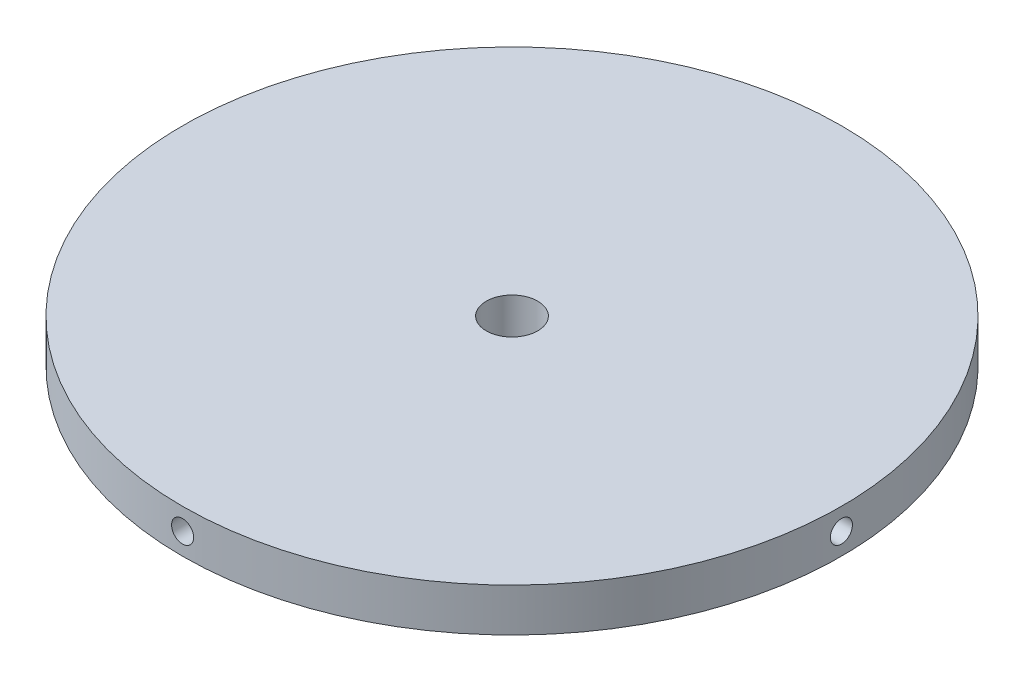
SolidWorks part; units mm, degrees
material "6061-T6 (SS)"
ref_plane "Front Plane" through (0, 0, 0) normal (0, 0, 1) x (1, 0, 0)
ref_plane "Top Plane" through (0, 0, 0) normal (0, 1, 0) x (1, 0, 0)
ref_plane "Right Plane" through (0, 0, 0) normal (1, 0, 0) x (0, 0, -1)
sketch "Sketch2" plane through (0, 0, 0) normal (0, 1, 0) x (1, 0, 0)
  circle A0 centre (0, 0) radius 76.1746
  dimension "D1" = 152.3492
extrude "Boss-Extrude1" add sketch "Sketch2" along normal blind 10
sketch "Sketch3" plane through (0, 10, 0) normal (0, 1, 0) x (1, 0, 0)
  circle A0 centre (0, 0) radius 5.9531
  dimension "D1" = 11.9062
extrude "Cut-Extrude1" cut sketch "Sketch3" against normal through all both and the other way through all
ref_plane "Plane2" through (0, 5, 0) normal (0, 1, 0) x (1, 0, 0)
sketch "Sketch7" plane through (0, 5, 0) normal (0, 1, 0) x (1, 0, 0)
  line L0 (-76.1746, 0) -> (76.1746, 0) construction
  line L1 (0, -76.1746) -> (0, 76.1746) construction
  circle A0 centre (0, 0) radius 76.1746 construction
  point P5 (-76.1746, 0)
  point P6 (0, 0)
  point P9 (0, 0)
ref_plane "Plane3" through (-76.1746, 0, 0) normal (1, 0, 0) x (0, 0, -1)
sketch "Sketch9" plane through (-76.1746, 0, 0) normal (1, 0, 0) x (0, 0, -1)
  point P0 (0, 5)
hole_wizard "1/4-20 Tapped Hole1" positions "Sketch9" profile "Sketch10" tap size "1/4-20" standard "ANSI Inch"
sketch "Sketch10" plane through (-76.1746, 5, 0) normal (0, 1, 0) x (0, 0, 1)
  line L0 (0, 0) -> (0, 26.9338)
  line L1 (0, 26.9338) -> (2.5527, 25.4)
  line L2 (2.5527, 25.4) -> (2.5527, 0)
  line L5 (2.5527, 0) -> (0, 0)
  line L10 (0, 26.9338) -> (-2.5527, 25.4) construction
  line L11 (0, -6.35) -> (0, 107.95) construction
  dimension "Tap Drill Dia." = 5.1054
  dimension "Tap Drill Depth" = 25.4
  dimension "Drill Angle" = 118
cosmetic thread "Hole Thread1" parameters "D1"=12.7, "D2"=6.35
pattern_circular "CirPattern2" count 4 over 270 about axis through (0, 10, 0) along (0, -1, 0) of "1/4-20 Tapped Hole1"
